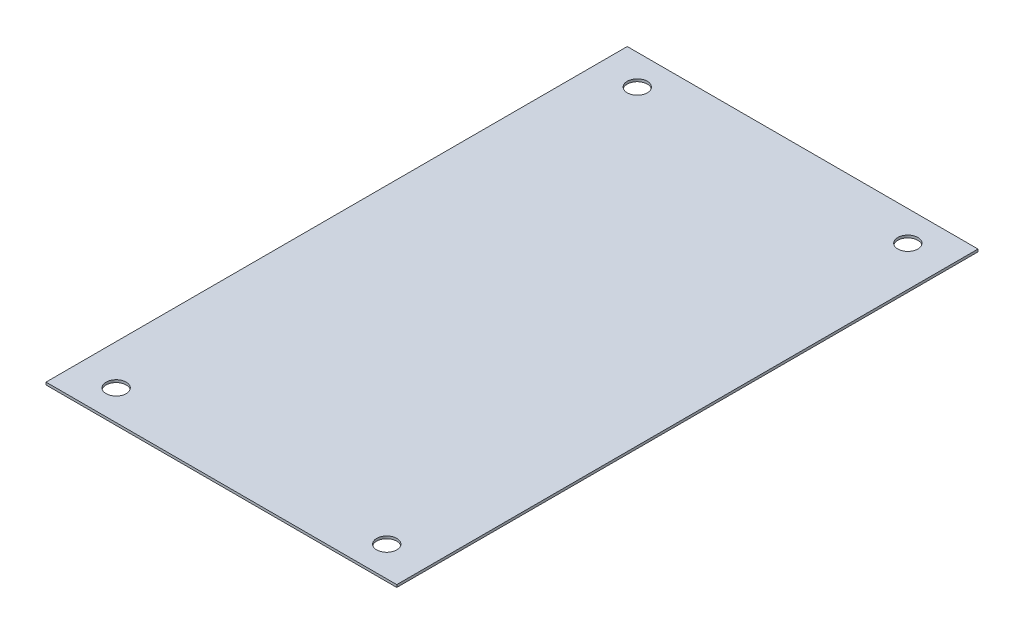
SolidWorks part; units mm, degrees
ref_plane "Front Plane" through (0, 0, 0) normal (0, 0, 1) x (1, 0, 0)
ref_plane "Top Plane" through (0, 0, 0) normal (0, 1, 0) x (1, 0, 0)
ref_plane "Right Plane" through (0, 0, 0) normal (1, 0, 0) x (0, 0, -1)
sketch "Sketch1" plane through (0, 0, 0) normal (0, 1, 0) x (1, 0, 0)
  line L1 (0, 0) -> (444.5, 0)
  line L2 (0, 0) -> (0, 736.6)
  line L3 (0, 736.6) -> (444.5, 736.6)
  line L4 (444.5, 0) -> (444.5, 736.6)
  dimension "D1" = 736.6
  dimension "D2" = 444.5
extrude "Boss-Extrude1" add sketch "Sketch1" along normal blind 3.175
hole_wizard "1 (1) Diameter Hole1" positions "Sketch3" profile "Sketch2" hole size "1" standard "Ansi Inch"
sketch "Sketch3" plane through (0, 3.175, 0) normal (0, 1, 0) x (-1, 0, 0)
  line L0 (0, 0) -> (-444.5, 0) construction
  line L1 (0, -368.3) -> (-444.5, -368.3) construction
  line L2 (0, -736.6) -> (0, 0) construction
  line L3 (-444.5, 0) -> (-444.5, -736.6) construction
  line L4 (-222.25, 0) -> (-222.25, -736.6) construction
  line L5 (-444.5, -736.6) -> (0, -736.6) construction
  point P0 (-50.8, -38.1)
  point P21 (-50.8, -698.5)
  point P23 (-393.7, -698.5)
  point P24 (-393.7, -38.1)
  dimension "D1" = 38.1
  dimension "D2" = 50.8
sketch "Sketch2" plane through (50.8, 3.175, -38.1) normal (1, 0, 0) x (0, 0, 1)
  line L0 (0, 0) -> (0, 28.2049)
  line L1 (0, 28.2049) -> (12.7, 20.574)
  line L2 (12.7, 20.574) -> (12.7, 0)
  line L5 (12.7, 0) -> (0, 0)
  line L10 (0, 28.2049) -> (-12.7, 20.574) construction
  line L11 (0, -6.35) -> (0, 107.95) construction
  dimension "Hole Dia." = 25.4
  dimension "Hole Depth" = 20.574
  dimension "Drill Angle" = 118
